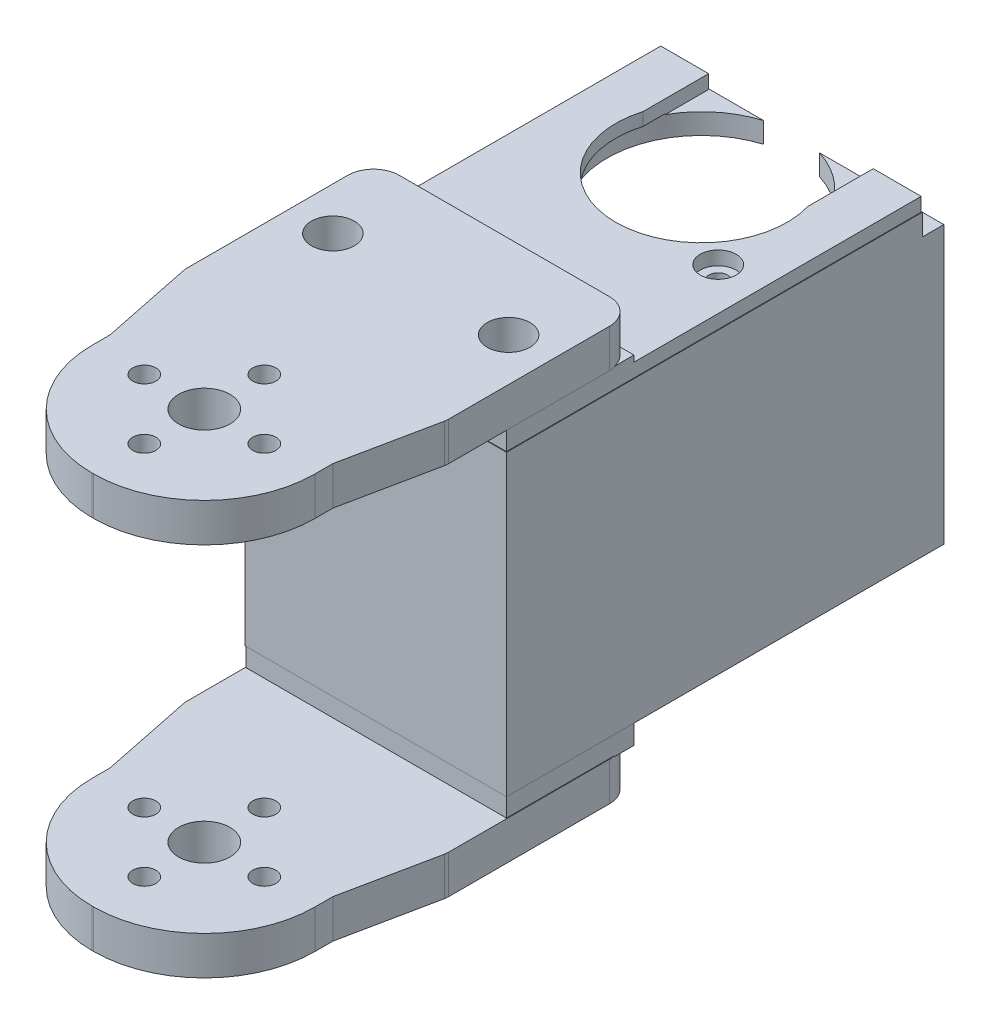
SolidWorks part; units mm, degrees
ref_plane "Front Plane" through (0, 0, 0) normal (0, 0, 1) x (1, 0, 0)
ref_plane "Top Plane" through (0, 0, 0) normal (0, 1, 0) x (1, 0, 0)
ref_plane "Right Plane" through (0, 0, 0) normal (1, 0, 0) x (0, 0, -1)
ref_plane "PY_m23_125" through (0, -23.125, 0) normal (0, 1, 0) x (1, 0, 0)
sketch "S_prism1" plane through (0, -23.125, 0) normal (0, 1, 0) x (1, 0, 0)
  line L0 (-13, 2) -> (-15.2191, 12.8008)
  line L1 (-15.26, 13.2033) -> (-15.26, 32)
  line L2 (-12.26, 35) -> (12.26, 35)
  line L3 (15.26, 32) -> (15.26, 13.2033)
  line L4 (15.2191, 12.8008) -> (13, 2)
  line L5 (13, 2) -> (13, -0.1)
  line L6 (0.1, -13) -> (-0.1, -13)
  line L7 (-13, -0.1) -> (-13, 2)
  arc A0 (-15.2191, 12.8008) -> (-15.26, 13.2033) centre (-13.2498, 13.2042) cw
  arc A1 (-15.26, 32) -> (-12.26, 35) centre (-12.2599, 31.9999) cw
  arc A2 (12.26, 35) -> (15.26, 32) centre (12.2599, 31.9999) cw
  arc A3 (15.26, 13.2033) -> (15.2191, 12.8008) centre (13.2498, 13.2042) cw
  arc A4 (13, -0.1) -> (0.1, -13) centre (0.1001, -0.1001) cw
  arc A5 (-0.1, -13) -> (-13, -0.1) centre (-0.1001, -0.1001) cw
extrude "Boss_1" add sketch "S_prism1" along normal blind 4.5
ref_plane "PY_p18_625" through (0, 18.625, 0) normal (0, 1, 0) x (1, 0, 0)
sketch "S_cyl2" plane through (0, 18.625, 0) normal (0, 1, 0) x (1, 0, 0)
  circle A0 centre (0, 0) radius 9
  dimension "D1_S_cyl2" = 18
extrude "Boss_2" add sketch "S_cyl2" along normal blind 2
ref_plane "PY_p20_625" through (0, 20.625, 0) normal (0, 1, 0) x (1, 0, 0)
sketch "S_prism3" plane through (0, 20.625, 0) normal (0, 1, 0) x (1, 0, 0)
  line L0 (-13, 2) -> (-15.2191, 12.8008)
  line L1 (-15.26, 13.2033) -> (-15.26, 32)
  line L2 (-12.26, 35) -> (12.26, 35)
  line L3 (15.26, 32) -> (15.26, 13.2033)
  line L4 (15.2191, 12.8008) -> (13, 2)
  line L5 (13, 2) -> (13, -0.1)
  line L6 (0.1, -13) -> (-0.1, -13)
  line L7 (-13, -0.1) -> (-13, 2)
  arc A0 (-15.2191, 12.8008) -> (-15.26, 13.2033) centre (-13.2498, 13.2042) cw
  arc A1 (-15.26, 32) -> (-12.26, 35) centre (-12.2599, 31.9999) cw
  arc A2 (12.26, 35) -> (15.26, 32) centre (12.2599, 31.9999) cw
  arc A3 (15.26, 13.2033) -> (15.2191, 12.8008) centre (13.2498, 13.2042) cw
  arc A4 (13, -0.1) -> (0.1, -13) centre (0.1001, -0.1001) cw
  arc A5 (-0.1, -13) -> (-13, -0.1) centre (-0.1001, -0.1001) cw
extrude "Boss_3" add sketch "S_prism3" along normal blind 4.5
ref_plane "PZ_m22_490" through (0, 0, -22.49) normal (0, 0, 1) x (1, 0, 0)
sketch "S_box4" plane through (0, 0, -22.49) normal (0, 0, 1) x (1, 0, 0)
  line L0 (-15.26, -16.4) -> (15.26, -16.4)
  line L1 (15.26, -16.4) -> (15.26, 18.4)
  line L2 (15.26, 18.4) -> (-15.26, 18.4)
  line L3 (-15.26, 18.4) -> (-15.26, -16.4)
  dimension "P1" = 15.26
  dimension "P2" = 16.4
  dimension "P3" = 15.26
  dimension "P4" = 16.4
  dimension "P5" = 15.26
  dimension "P6" = 18.4
  dimension "P7" = 15.26
  dimension "P8" = 18.4
extrude "Boss_4" add sketch "S_box4" along normal blind 2.5
ref_plane "PZ_m71_010" through (0, 0, -71.01) normal (0, 0, 1) x (1, 0, 0)
sketch "S_box5" plane through (0, 0, -71.01) normal (0, 0, 1) x (1, 0, 0)
  line L0 (12.76, -16.4) -> (15.26, -16.4)
  line L1 (15.26, -16.4) -> (15.26, 18.4)
  line L2 (15.26, 18.4) -> (12.76, 18.4)
  line L3 (12.76, 18.4) -> (12.76, -16.4)
  dimension "P1" = 12.76
  dimension "P2" = 16.4
  dimension "P3" = 15.26
  dimension "P4" = 16.4
  dimension "P5" = 15.26
  dimension "P6" = 18.4
  dimension "P7" = 12.76
  dimension "P8" = 18.4
extrude "Boss_5" add sketch "S_box5" along normal blind 51.02
sketch "S_box6" plane through (0, 0, -71.01) normal (0, 0, 1) x (1, 0, 0)
  line L0 (-15.26, 16) -> (15.26, 16)
  line L1 (15.26, 16) -> (15.26, 18.4)
  line L2 (15.26, 18.4) -> (-15.26, 18.4)
  line L3 (-15.26, 18.4) -> (-15.26, 16)
  dimension "P1" = 15.26
  dimension "P2" = 16
  dimension "P3" = 15.26
  dimension "P4" = 16
  dimension "P5" = 15.26
  dimension "P6" = 18.4
  dimension "P7" = 15.26
  dimension "P8" = 18.4
extrude "Boss_6" add sketch "S_box6" along normal blind 51.02
ref_plane "PZ_m38_000" through (0, 0, -38) normal (0, 0, 1) x (1, 0, 0)
sketch "S_box7" plane through (0, 0, -38) normal (0, 0, 1) x (1, 0, 0)
  line L0 (-15.26, -16.4) -> (-12.76, -16.4)
  line L1 (-12.76, -16.4) -> (-12.76, 18.4)
  line L2 (-12.76, 18.4) -> (-15.26, 18.4)
  line L3 (-15.26, 18.4) -> (-15.26, -16.4)
  dimension "P1" = 15.26
  dimension "P2" = 16.4
  dimension "P3" = 12.76
  dimension "P4" = 16.4
  dimension "P5" = 12.76
  dimension "P6" = 18.4
  dimension "P7" = 15.26
  dimension "P8" = 18.4
extrude "Boss_7" add sketch "S_box7" along normal blind 18.01
ref_plane "PZ_m34_930" through (0, 0, -34.93) normal (0, 0, 1) x (1, 0, 0)
sketch "S_box8" plane through (0, 0, -34.93) normal (0, 0, 1) x (1, 0, 0)
  line L0 (-15.19, -18.725) -> (15.19, -18.725)
  line L1 (15.19, -18.725) -> (15.19, -16.05)
  line L2 (15.19, -16.05) -> (-15.19, -16.05)
  line L3 (-15.19, -16.05) -> (-15.19, -18.725)
  dimension "P1" = 15.19
  dimension "P2" = 18.725
  dimension "P3" = 15.19
  dimension "P4" = 18.725
  dimension "P5" = 15.19
  dimension "P6" = 16.05
  dimension "P7" = 15.19
  dimension "P8" = 16.05
extrude "Boss_8" add sketch "S_box8" along normal blind 14.87
sketch "S_box9" plane through (0, 0, -34.93) normal (0, 0, 1) x (1, 0, 0)
  line L0 (-15.19, 18.3) -> (15.19, 18.3)
  line L1 (15.19, 18.3) -> (15.19, 20.725)
  line L2 (15.19, 20.725) -> (-15.19, 20.725)
  line L3 (-15.19, 20.725) -> (-15.19, 18.3)
  dimension "P1" = 15.19
  dimension "P2" = 18.3
  dimension "P3" = 15.19
  dimension "P4" = 18.3
  dimension "P5" = 15.19
  dimension "P6" = 20.725
  dimension "P7" = 15.19
  dimension "P8" = 20.725
extrude "Boss_9" add sketch "S_box9" along normal blind 14.87
ref_plane "PZ_m58_000" through (0, 0, -58) normal (0, 0, 1) x (1, 0, 0)
sketch "S_box10" plane through (0, 0, -58) normal (0, 0, 1) x (1, 0, 0)
  line L0 (-15.19, 18.35) -> (15.19, 18.35)
  line L1 (15.19, 18.35) -> (15.19, 20)
  line L2 (15.19, 20) -> (-15.19, 20)
  line L3 (-15.19, 20) -> (-15.19, 18.35)
  dimension "P1" = 15.19
  dimension "P2" = 18.35
  dimension "P3" = 15.19
  dimension "P4" = 18.35
  dimension "P5" = 15.19
  dimension "P6" = 20
  dimension "P7" = 15.19
  dimension "P8" = 20
extrude "Boss_10" add sketch "S_box10" along normal blind 37.94
ref_plane "PZ_m68_440" through (0, 0, -68.44) normal (0, 0, 1) x (1, 0, 0)
sketch "S_box11" plane through (0, 0, -68.44) normal (0, 0, 1) x (1, 0, 0)
  line L0 (-15.19, 18.35) -> (-9.6, 18.35)
  line L1 (-9.6, 18.35) -> (-9.6, 20)
  line L2 (-9.6, 20) -> (-15.19, 20)
  line L3 (-15.19, 20) -> (-15.19, 18.35)
  dimension "P1" = 15.19
  dimension "P2" = 18.35
  dimension "P3" = 9.6
  dimension "P4" = 18.35
  dimension "P5" = 9.6
  dimension "P6" = 20
  dimension "P7" = 15.19
  dimension "P8" = 20
extrude "Boss_11" add sketch "S_box11" along normal blind 10.54
sketch "S_box12" plane through (0, 0, -68.44) normal (0, 0, 1) x (1, 0, 0)
  line L0 (9.6, 18.35) -> (15.19, 18.35)
  line L1 (15.19, 18.35) -> (15.19, 20)
  line L2 (15.19, 20) -> (9.6, 20)
  line L3 (9.6, 20) -> (9.6, 18.35)
  dimension "P1" = 9.6
  dimension "P2" = 18.35
  dimension "P3" = 15.19
  dimension "P4" = 18.35
  dimension "P5" = 15.19
  dimension "P6" = 20
  dimension "P7" = 9.6
  dimension "P8" = 20
extrude "Boss_12" add sketch "S_box12" along normal blind 10.54
ref_plane "PY_m23_225" through (0, -23.225, 0) normal (0, 1, 0) x (1, 0, 0)
sketch "S_hole13" plane through (0, -23.225, 0) normal (0, 1, 0) x (1, 0, 0)
  circle A0 centre (0, 0) radius 3
  dimension "D1_S_hole13" = 6
extrude "Hole_13" cut sketch "S_hole13" along normal blind 4.7
sketch "S_hole14" plane through (0, -23.225, 0) normal (0, 1, 0) x (1, 0, 0)
  circle A0 centre (7, 0) radius 1.35
  dimension "D1_S_hole14" = 2.7
  dimension "P2" = 7
extrude "Hole_14" cut sketch "S_hole14" along normal blind 4.7
sketch "S_hole15" plane through (0, -23.225, 0) normal (0, 1, 0) x (1, 0, 0)
  circle A0 centre (0, -7) radius 1.35
  dimension "D1_S_hole15" = 2.7
  dimension "P2" = 7
extrude "Hole_15" cut sketch "S_hole15" along normal blind 4.7
sketch "S_hole16" plane through (0, -23.225, 0) normal (0, 1, 0) x (1, 0, 0)
  circle A0 centre (-7, 0) radius 1.35
  dimension "D1_S_hole16" = 2.7
  dimension "P2" = 7
extrude "Hole_16" cut sketch "S_hole16" along normal blind 4.7
sketch "S_hole17" plane through (0, -23.225, 0) normal (0, 1, 0) x (1, 0, 0)
  circle A0 centre (0, 7) radius 1.35
  dimension "D1_S_hole17" = 2.7
  dimension "P2" = 7
extrude "Hole_17" cut sketch "S_hole17" along normal blind 4.7
ref_plane "PY_p18_525" through (0, 18.525, 0) normal (0, 1, 0) x (1, 0, 0)
sketch "S_hole18" plane through (0, 18.525, 0) normal (0, 1, 0) x (1, 0, 0)
  circle A0 centre (0, 0) radius 3
  dimension "D1_S_hole18" = 6
extrude "Hole_18" cut sketch "S_hole18" along normal blind 6.7
sketch "S_hole19" plane through (0, 18.525, 0) normal (0, 1, 0) x (1, 0, 0)
  circle A0 centre (7, 0) radius 1.35
  dimension "D1_S_hole19" = 2.7
  dimension "P2" = 7
extrude "Hole_19" cut sketch "S_hole19" along normal blind 6.7
sketch "S_hole20" plane through (0, 18.525, 0) normal (0, 1, 0) x (1, 0, 0)
  circle A0 centre (0, -7) radius 1.35
  dimension "D1_S_hole20" = 2.7
  dimension "P2" = 7
extrude "Hole_20" cut sketch "S_hole20" along normal blind 6.7
sketch "S_hole21" plane through (0, 18.525, 0) normal (0, 1, 0) x (1, 0, 0)
  circle A0 centre (-7, 0) radius 1.35
  dimension "D1_S_hole21" = 2.7
  dimension "P2" = 7
extrude "Hole_21" cut sketch "S_hole21" along normal blind 6.7
sketch "S_hole22" plane through (0, 18.525, 0) normal (0, 1, 0) x (1, 0, 0)
  circle A0 centre (0, 7) radius 1.35
  dimension "D1_S_hole22" = 2.7
  dimension "P2" = 7
extrude "Hole_22" cut sketch "S_hole22" along normal blind 6.7
ref_plane "PY_p15_900" through (0, 15.9, 0) normal (0, 1, 0) x (1, 0, 0)
sketch "S_hole23" plane through (0, 15.9, 0) normal (0, 1, 0) x (1, 0, 0)
  circle A0 centre (0, 58) radius 11
  dimension "D1_S_hole23" = 22
  dimension "P2" = 58
extrude "Hole_23" cut sketch "S_hole23" along normal blind 2.6
sketch "S_hole24" plane through (0, 15.9, 0) normal (0, 1, 0) x (1, 0, 0)
  circle A0 centre (10.25, 49.7) radius 1.1
  dimension "D1_S_hole24" = 2.2
  dimension "P2" = 10.25
  dimension "P3" = 49.7
extrude "Hole_24" cut sketch "S_hole24" along normal blind 2.6
sketch "S_hole25" plane through (0, 15.9, 0) normal (0, 1, 0) x (1, 0, 0)
  circle A0 centre (-10.25, 25.25) radius 1.1
  dimension "D1_S_hole25" = 2.2
  dimension "P2" = 10.25
  dimension "P3" = 25.25
extrude "Hole_25" cut sketch "S_hole25" along normal blind 2.6
sketch "S_hole26" plane through (0, 15.9, 0) normal (0, 1, 0) x (1, 0, 0)
  circle A0 centre (10.25, 25.25) radius 1.1
  dimension "D1_S_hole26" = 2.2
  dimension "P2" = 10.25
  dimension "P3" = 25.25
extrude "Hole_26" cut sketch "S_hole26" along normal blind 2.6
ref_plane "PZ_m71_110" through (0, 0, -71.11) normal (0, 0, 1) x (1, 0, 0)
sketch "S_cut27" plane through (0, 0, -71.11) normal (0, 0, 1) x (1, 0, 0)
  line L0 (-15.36, 15.9) -> (15.36, 15.9)
  line L1 (15.36, 15.9) -> (15.36, 18.5)
  line L2 (15.36, 18.5) -> (-15.36, 18.5)
  line L3 (-15.36, 18.5) -> (-15.36, 15.9)
  dimension "P1" = 15.36
  dimension "P2" = 15.9
  dimension "P3" = 15.36
  dimension "P4" = 15.9
  dimension "P5" = 15.36
  dimension "P6" = 18.5
  dimension "P7" = 15.36
  dimension "P8" = 18.5
extrude "Pocket_27" cut sketch "S_cut27" along normal blind 2.6
ref_plane "PY_p20_050" through (0, 20.05, 0) normal (0, 1, 0) x (1, 0, 0)
sketch "S_hole28" plane through (0, 20.05, 0) normal (0, 1, 0) x (1, 0, 0)
  circle A0 centre (-10.25, 25.25) radius 2.5
  dimension "D1_S_hole28" = 5
  dimension "P2" = 10.25
  dimension "P3" = 25.25
extrude "Hole_28" cut sketch "S_hole28" along normal blind 5.175
sketch "S_hole29" plane through (0, 20.05, 0) normal (0, 1, 0) x (1, 0, 0)
  circle A0 centre (10.25, 25.25) radius 2.5
  dimension "D1_S_hole29" = 5
  dimension "P2" = 10.25
  dimension "P3" = 25.25
extrude "Hole_29" cut sketch "S_hole29" along normal blind 5.175
ref_plane "PY_p18_300" through (0, 18.3, 0) normal (0, 1, 0) x (1, 0, 0)
sketch "S_hole30" plane through (0, 18.3, 0) normal (0, 1, 0) x (1, 0, 0)
  circle A0 centre (0, 58) radius 10
  dimension "D1_S_hole30" = 20
  dimension "P2" = 58
extrude "Hole_30" cut sketch "S_hole30" along normal blind 1.8
sketch "S_hole31" plane through (0, 18.3, 0) normal (0, 1, 0) x (1, 0, 0)
  circle A0 centre (10.25, 49.7) radius 1.1
  dimension "D1_S_hole31" = 2.2
  dimension "P2" = 10.25
  dimension "P3" = 49.7
extrude "Hole_31" cut sketch "S_hole31" along normal blind 1.8
ref_plane "PY_p18_400" through (0, 18.4, 0) normal (0, 1, 0) x (1, 0, 0)
sketch "S_hole32" plane through (0, 18.4, 0) normal (0, 1, 0) x (1, 0, 0)
  circle A0 centre (10.25, 49.7) radius 2.1
  dimension "D1_S_hole32" = 4.2
  dimension "P2" = 10.25
  dimension "P3" = 49.7
extrude "Hole_32" cut sketch "S_hole32" along normal blind 1.7
sketch "S_hole33" plane through (0, 18.3, 0) normal (0, 1, 0) x (1, 0, 0)
  circle A0 centre (-10.25, 25.25) radius 1.1
  dimension "D1_S_hole33" = 2.2
  dimension "P2" = 10.25
  dimension "P3" = 25.25
extrude "Hole_33" cut sketch "S_hole33" along normal blind 1.8
sketch "S_hole34" plane through (0, 18.4, 0) normal (0, 1, 0) x (1, 0, 0)
  circle A0 centre (-10.25, 25.25) radius 2.1
  dimension "D1_S_hole34" = 4.2
  dimension "P2" = 10.25
  dimension "P3" = 25.25
extrude "Hole_34" cut sketch "S_hole34" along normal blind 1.7
sketch "S_hole35" plane through (0, 18.3, 0) normal (0, 1, 0) x (1, 0, 0)
  circle A0 centre (10.25, 25.25) radius 1.1
  dimension "D1_S_hole35" = 2.2
  dimension "P2" = 10.25
  dimension "P3" = 25.25
extrude "Hole_35" cut sketch "S_hole35" along normal blind 1.8
sketch "S_hole36" plane through (0, 18.4, 0) normal (0, 1, 0) x (1, 0, 0)
  circle A0 centre (10.25, 25.25) radius 2.1
  dimension "D1_S_hole36" = 4.2
  dimension "P2" = 10.25
  dimension "P3" = 25.25
extrude "Hole_36" cut sketch "S_hole36" along normal blind 1.7
equation "\"plate_t\" = 3"
equation "\"clearance\" = 0.4"
